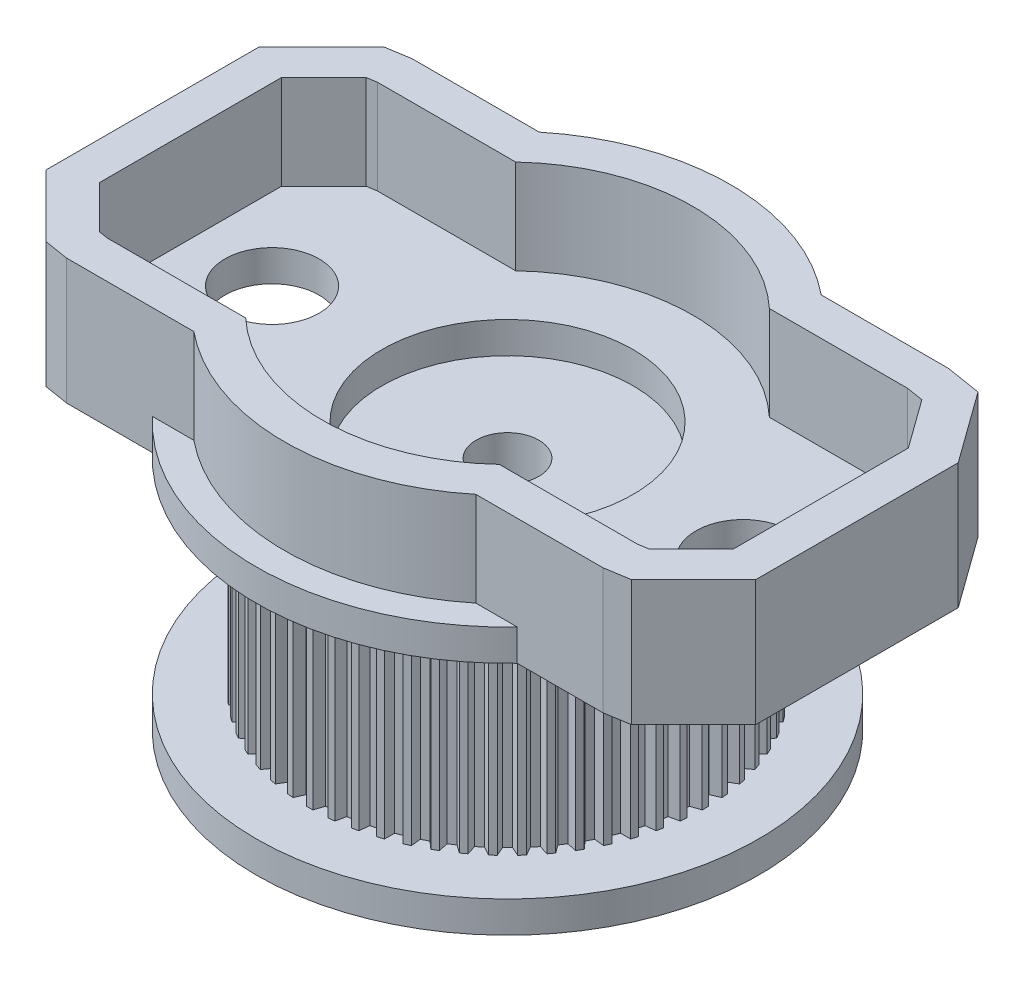
SolidWorks part; units mm, degrees
ref_plane "Front Plane" through (0, 0, 0) normal (0, 0, 1) x (1, 0, 0)
ref_plane "Top Plane" through (0, 0, 0) normal (0, 1, 0) x (1, 0, 0)
ref_plane "Right Plane" through (0, 0, 0) normal (1, 0, 0) x (0, 0, -1)
sketch "Sketch1" plane through (0, 0, 0) normal (0, 1, 0) x (1, 0, 0)
  line L1 (1.95, 3.3775) -> (-1.95, 3.3775)
  line L2 (-1.95, 3.3775) -> (-3.9, 0)
  line L3 (-3.9, 0) -> (-1.95, -3.3775)
  line L4 (-1.95, -3.3775) -> (1.95, -3.3775)
  line L5 (1.95, -3.3775) -> (3.9, 0)
  line L6 (3.9, 0) -> (1.95, 3.3775)
  circle A0 centre (0, 0) radius 3.9 construction
  circle A1 centre (0, 0) radius 3.3775 construction
  dimension "D1" = 7.8
extrude "Boss-Extrude1" add sketch "Sketch1" along normal blind 4
sketch "Sketch2" plane through (0, 4, 0) normal (0, 1, 0) x (1, 0, 0)
  circle A0 centre (0, 0) radius 8
  circle A1 centre (0, 0) radius 5
  line M3 (3.9, 0) -> (1.95, 3.3775)
  line M4 (1.95, 3.3775) -> (-1.95, 3.3775)
  line M5 (-1.95, 3.3775) -> (-3.9, 0)
  line M6 (-3.9, 0) -> (-1.95, -3.3775)
  line M7 (-1.95, -3.3775) -> (1.95, -3.3775)
  line M8 (1.95, -3.3775) -> (3.9, 0)
  dimension "D1" = 16
  dimension "D2" = 10
extrude "Boss-Extrude2" add sketch "Sketch2" along normal blind 1 separate body contours A1 M3 M8 M7 M6 M5 M4 | M8 M3 M4 M5 M6 M7 | A0 A1 | A1 | A0 region at (-7.7737, 4, 0) region at (-4.8586, 4, 0) region at (0, 4, 0)
sketch "Sketch4" plane through (0, 5, 0) normal (0, 1, 0) x (1, 0, 0)
  circle A0 centre (0, 0) radius 6
  dimension "D1" = 12
extrude "Boss-Extrude3" add sketch "Sketch4" along normal blind 6.5
sketch "Sketch5" plane through (0, 11.5, 0) normal (0, 1, 0) x (1, 0, 0)
  line L0 (0, 0) -> (0, 6) construction
  line L1 (-0.2, 5.9967) -> (-0.1, 6.3)
  line L2 (-0.1, 6.3) -> (0.1, 6.3)
  line L3 (0.1, 6.3) -> (0.2, 5.9967)
  line L4 (0, 6.3) -> (0, 6) construction
  circle A1 centre (0, 0) radius 6
  arc A2 (0.2, 5.9967) -> (-0.2, 5.9967) centre (0, 0) ccw
  dimension "D2" = 0.3
  dimension "D3" = 0.2
  dimension "D4" = 0.2
  dimension "D5" = 0.2
  dimension "D1" = 0
extrude "Boss-Extrude4" add sketch "Sketch5" against normal up to surface (6.5 mm away) up to face at (0, 5, 6)
pattern_circular "CirPattern1" count 60 over 360 about axis through (0, 11.5, 0) along (0, -1, 0) of "Boss-Extrude4"
sketch "Sketch6" plane through (0, 11.5, 0) normal (0, 1, 0) x (1, 0, 0)
  circle A0 centre (0, 0) radius 8
  dimension "D1" = 16
extrude "Boss-Extrude5" add sketch "Sketch6" along normal blind 1
sketch "Sketch12" plane through (0, 0, 0) normal (0, -1, 0) x (1, 0, 0)
  line L6 (1.95, -3.3775) -> (3.9, 0)
  line L7 (3.9, 0) -> (1.95, 3.3775)
  line L8 (1.95, 3.3775) -> (-1.95, 3.3775)
  line L9 (-1.95, 3.3775) -> (-3.9, 0)
  line L10 (-3.9, 0) -> (-1.95, -3.3775)
  line L11 (-1.95, -3.3775) -> (1.95, -3.3775)
  line L12 (1.95, -3.3775) -> (3.9, 0)
  line L13 (3.9, 0) -> (1.95, 3.3775)
  line L14 (1.95, 3.3775) -> (-1.95, 3.3775)
  line L15 (-1.95, 3.3775) -> (-3.9, 0)
  line L16 (-3.9, 0) -> (-1.95, -3.3775)
  line L17 (-1.95, -3.3775) -> (1.95, -3.3775)
  dimension "D1" = 0
extrude "Cut-Extrude3" cut sketch "Sketch12" against normal up to surface (4 mm away) up to face at (0, 4, 8)
sketch "Sketch14" plane through (0, 4, 0) normal (0, -1, 0) x (1, 0, 0)
  circle A0 centre (0, 0) radius 1
  dimension "D1" = 2
extrude "Cut-Extrude4" cut sketch "Sketch14" against normal blind 10
sketch "Sketch15" plane through (0, 4, 0) normal (0, -1, 0) x (1, 0, 0)
  circle A0 centre (0, 0) radius 3
  dimension "D1" = 6
extrude "Cut-Extrude5" cut sketch "Sketch15" against normal blind 5.5
chamfer "Chamfer1" distance 0.5 angle 45 1 edges at (0, 4, -3)
sketch "Sketch16" plane through (0, 12.5, 0) normal (0, 1, 0) x (1, 0, 0)
  line L0 (-8.4192, 4) -> (-8.6072, 3.9696)
  line L1 (-8.6072, 3.9696) -> (-9.8, 2.7768)
  line L2 (-9.8, 2.7768) -> (-9.8, -2.7768)
  line L3 (-9.8, -2.7768) -> (-8.6072, -3.9696)
  line L4 (-8.6072, -3.9696) -> (-8.4192, -4)
  line L5 (-8.4192, -4) -> (-3.9192, -4)
  line L6 (3.9192, -4) -> (8.4192, -4)
  line L7 (8.4192, -4) -> (8.6072, -3.9696)
  line L8 (8.6072, -3.9696) -> (9.8, -2.7768)
  line L9 (9.8, -2.7768) -> (9.8, 2.5686)
  line L10 (9.8, 2.5686) -> (8.8128, 3.9364)
  line L11 (8.8128, 3.9364) -> (8.4192, 4)
  line L12 (8.4192, 4) -> (3.9192, 4)
  line L13 (-3.9192, 4) -> (-8.4192, 4)
  line L14 (-7.5, 0) -> (7.5, 0) construction
  line L15 (-8.4433, 4.3) -> (-8.7508, 4.2503)
  line L16 (-8.7508, 4.2503) -> (-10.1, 2.9011)
  line L17 (-10.1, 2.9011) -> (-10.1, -2.9011)
  line L18 (-10.1, -2.9011) -> (-8.7508, -4.2503)
  line L19 (-8.7508, -4.2503) -> (-8.4433, -4.3)
  line L20 (-8.4433, -4.3) -> (-4.0398, -4.3)
  line L21 (4.0398, -4.3) -> (8.4433, -4.3)
  line L22 (8.4433, -4.3) -> (8.7508, -4.2503)
  line L23 (8.7508, -4.2503) -> (10.1, -2.9011)
  line L24 (10.1, -2.9011) -> (10.1, 2.6656)
  line L25 (10.1, 2.6656) -> (8.9833, 4.2127)
  line L26 (8.9833, 4.2127) -> (8.4433, 4.3)
  line L27 (8.4433, 4.3) -> (4.0398, 4.3)
  line L28 (-4.0398, 4.3) -> (-8.4433, 4.3)
  line L29 (-4.49, 5.5) -> (-8.5396, 5.5)
  line L30 (-8.5396, 5.5) -> (-9.3251, 5.3731)
  line L31 (-9.3251, 5.3731) -> (-11.3, 3.3982)
  line L32 (-11.3, 3.3982) -> (-11.3, -3.3982)
  line L33 (-11.3, -3.3982) -> (-9.3251, -5.3731)
  line L34 (-9.3251, -5.3731) -> (-8.5396, -5.5)
  line L35 (-8.5396, -5.5) -> (-4.49, -5.5)
  line L36 (4.49, -5.5) -> (8.5396, -5.5)
  line L37 (8.5396, -5.5) -> (9.3251, -5.3731)
  line L38 (9.3251, -5.3731) -> (11.3, -3.3982)
  line L39 (11.3, -3.3982) -> (11.3, 3.0534)
  line L40 (11.3, 3.0534) -> (9.6655, 5.318)
  line L41 (9.6655, 5.318) -> (8.5396, 5.5)
  line L42 (8.5396, 5.5) -> (4.49, 5.5)
  circle A0 centre (-7.5, 0) radius 1.5
  arc A1 (-3.9192, -4) -> (3.9192, -4) centre (0, 0) ccw
  arc A2 (3.9192, 4) -> (-3.9192, 4) centre (0, 0) ccw
  circle A3 centre (7.5, 0) radius 1.5
  circle A4 centre (0, 0) radius 1.5
  circle A6 centre (0, 0) radius 1 construction
  circle A7 centre (0, 0) radius 1 construction
  arc A8 (-4.0398, -4.3) -> (4.0398, -4.3) centre (0, 0) ccw
  arc A9 (4.0398, 4.3) -> (-4.0398, 4.3) centre (0, 0) ccw
  arc A10 (4.49, 5.5) -> (-4.49, 5.5) centre (0, 0) ccw
  arc A11 (-4.49, -5.5) -> (4.49, -5.5) centre (0, 0) ccw
  circle M23 centre (0, 0) radius 8
  dimension "D1" = 3
  dimension "D3" = 3
  dimension "D4" = 3
  dimension "D5" = 5.6
  dimension "D6" = 5.6
  dimension "D2" = 15
  dimension "D7" = 3.9192
  dimension "D8" = 3.9192
  dimension "D9" = 7.5
  dimension "D10" = 8.6072
  dimension "D11" = 8.4192
  dimension "D12" = 8.4192
  dimension "D13" = 8.8128
  dimension "D14" = 9.8
  dimension "D15" = 2.5686
  dimension "D16" = 2.7768
  dimension "D17" = 9.8
  dimension "D18" = 3.9364
  dimension "D19" = 3.9192
  dimension "D20" = 3.9192
  dimension "D21" = 8.4192
  dimension "D22" = 8.4192
  dimension "D23" = 8.6072
  dimension "D24" = 8.6072
  dimension "D25" = 9.8
  dimension "D26" = 9.8
  dimension "D27" = 3.9696
  dimension "D28" = 2.7768
  dimension "D29" = 4
  dimension "D30" = 0.3
  dimension "D31" = 1.2
  dimension "D32" = 4
  dimension "D33" = 4
  dimension "D35" = 2.7768
  dimension "D36" = 3.9696
  dimension "D37" = 3.9696
  dimension "D38" = 4
  dimension "D39" = 4
extrude "Boss-Extrude6" add sketch "Sketch16" along normal blind 3 contours L35 A11 L36 L21 A8 L20 M23 | L41 L42 L27 L26 L25 L24 L23 L22 L21 L36 L37 L38 L39 L40 M23 | L42 A10 L29 L28 A9 L27 M23 | L34 L35 L20 L19 L18 L17 L16 L15 L28 L29 L30 L31 L32 L33 M23 region at (-6.1978, 12.5, -4.8375) region at (-7.5947, 12.5, -4.4229) region at (7.1745, 12.5, -5.3771) region at (-5.393, 12.5, 4.4378)
sketch "Sketch17" plane through (0, 12.5, 0) normal (0, 1, 0) x (1, 0, 0)
  circle A0 centre (0, 0) radius 4
  dimension "D1" = 8
extrude "Cut-Extrude6" cut sketch "Sketch17" against normal blind 1
extrude "Boss-Extrude7" add sketch "Sketch16<4>" against normal blind 1 contours A0 L13 L0 L1 L2 L3 L4 L5 M23 | A3 L6 L7 L8 L9 L10 L11 L12 M23 | L26 L27 L12 L11 L10 L9 L8 L7 L6 L21 L22 L23 L24 L25 M23 | L41 L42 L27 L26 L25 L24 L23 L22 L21 L36 L37 L38 L39 L40 M23 | L34 L35 L20 L19 L18 L17 L16 L15 L28 L29 L30 L31 L32 L33 M23 | L28 L15 L16 L17 L18 L19 L20 L5 L4 L3 L2 L1 L0 L13 M23 region at (-7.6737, 12.5, -3.915) region at (-8.5279, 12.5, -4.0759) region at (-7.5947, 12.5, -4.4229) region at (6.9177, 12.5, -4.1989) region at (7.6737, 12.5, -3.915) region at (7.1745, 12.5, -5.3771)
sketch "Sketch16<4>" plane through (0, 12.5, 0) normal (0, 1, 0) x (1, 0, 0) same geometry as "Sketch16"
extrude "Cut-Extrude7" cut sketch "Sketch16<5>" against normal blind 1 contours A0 M23 | A3 M23 region at (-7.1021, 12.5, 0) region at (7.1021, 12.5, 0)
sketch "Sketch16<5>" plane through (0, 12.5, 0) normal (0, 1, 0) x (1, 0, 0) same geometry as "Sketch16"
